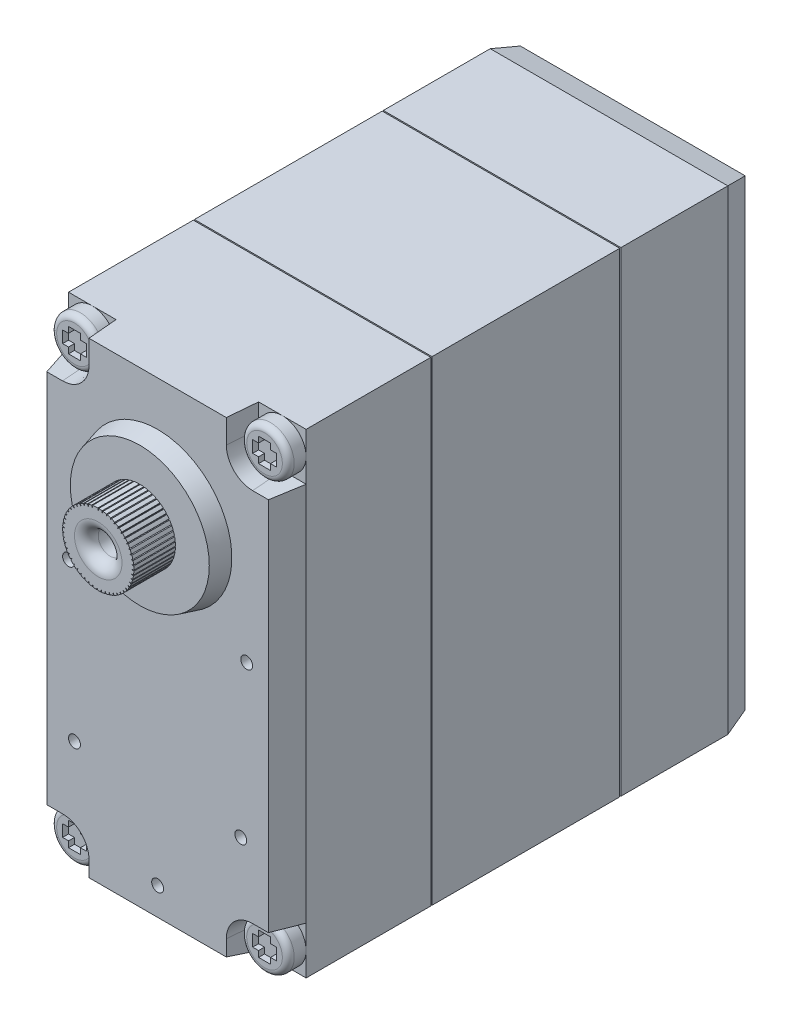
SolidWorks part; units mm, degrees
ref_plane "Front Plane" through (0, 0, 0) normal (0, 0, 1) x (1, 0, 0)
ref_plane "Top Plane" through (0, 0, 0) normal (0, 1, 0) x (1, 0, 0)
ref_plane "Right Plane" through (0, 0, 0) normal (1, 0, 0) x (0, 0, -1)
sketch "Sketch1" plane through (0, 0, 0) normal (0, 0, 1) x (1, 0, 0)
  line L1 (10, 20) -> (-10, 20)
  line L2 (10, 20) -> (10, -20)
  line L3 (10, -20) -> (-10, -20)
  line L4 (-10, 20) -> (-10, -20)
  line L5 (10, 20) -> (-10, -20) construction
  line L6 (10, -20) -> (-10, 20) construction
  point P0 (0, 0)
  dimension "D1" = 20
  dimension "D2" = 40
extrude "Boss-Extrude1" add sketch "Sketch1" along normal blind 40
sketch "Sketch2" plane through (0, 0, 40) normal (0, 0, 1) x (1, 0, 0)
  circle A0 centre (0, 10) radius 3
extrude "Boss-Extrude2" add sketch "Sketch2" along normal blind 5
sketch "Sketch3" plane through (0, 0, 40) normal (0, 0, 1) x (1, 0, 0)
  circle A0 centre (0, 10) radius 6.25
  dimension "D1" = 12.5
extrude "Boss-Extrude3" add sketch "Sketch3" along normal blind 1.5
sketch "Sketch4" plane through (0, 0, 0) normal (0, 0, -1) x (-1, 0, 0)
  circle A0 centre (0, 10) radius 3
extrude "Boss-Extrude4" add sketch "Sketch4" along normal blind 5
sketch "Sketch5" plane through (0, 0, 0) normal (0, 0, -1) x (-1, 0, 0)
  circle A0 centre (0, 10) radius 6.25
extrude "Boss-Extrude5" add sketch "Sketch5" along normal blind 1.5
chamfer "Chamfer1" distance 1.5 angle 15 2 edges at (6.25, 10, 41.5) (-6.25, 10, -1.5) first distance on face at (6.25, 10, 41.5) first distance on face at (-6.25, 10, -1.5)
sketch "Sketch6" plane through (0, 0, 40) normal (0, 0, 1) x (1, 0, 0)
  circle A0 centre (0, 10) radius 1
extrude "Cut-Extrude1" cut sketch "Sketch6" along normal blind 8.5
sketch "Sketch7" plane through (0, 0, 0) normal (0, 0, -1) x (-1, 0, 0)
  circle A0 centre (0, 10) radius 1
extrude "Cut-Extrude2" cut sketch "Sketch7" along normal blind 8.5
fillet "Fillet1" radius 0.2 1 edges at (-3, 10, -5)
sketch "Sketch8" plane through (0, 0, 0) normal (0, 0, -1) x (-1, 0, 0)
  line L5 (7.5, -2.5) -> (-7.5, -17.5) construction
  line L6 (7.5, -17.5) -> (-7.5, -2.5) construction
  circle A0 centre (-7.5, -17.5) radius 0.5
  circle A1 centre (7.5, -17.5) radius 0.5
  circle A2 centre (7.5, -2.5) radius 0.5
  circle A3 centre (-7.5, -2.5) radius 0.5
  point P0 (0, -10)
  dimension "D2" = 15
  dimension "D3" = 15
extrude "Cut-Extrude3" cut sketch "Sketch8" against normal blind 1
sketch "Sketch9" plane through (0, 0, 40) normal (0, 0, 1) x (1, 0, 0)
  circle A1 centre (-7, -10) radius 0.5
  circle A2 centre (7, -10) radius 0.5
  circle A3 centre (0, -17) radius 0.5
  circle A4 centre (-7.5, 3) radius 0.5
  circle A5 centre (7.5, 3) radius 0.5
  point P12 (0, -10)
  point P15 (0, -10)
extrude "Cut-Extrude4" cut sketch "Sketch9" against normal blind 1
sketch "Sketch10" plane through (0, 0, 41.5) normal (0, 0, 1) x (1, 0, 0)
  line L3 (-0.0094, 12.8532) -> (-0.0352, 12.9998)
  line L4 (0.0103, 12.853) -> (0.0388, 12.9997)
  arc A4 (0.0388, 12.9997) -> (-0.0352, 12.9998) centre (0, 10) ccw
  arc A5 (-0.0094, 12.8532) -> (0.0103, 12.853) centre (0.0005, 12.8549) ccw
  dimension "D1" = 0.01
extrude "Cut-Extrude6" cut sketch "Sketch10" along normal blind 10
ref_axis "Axis1" through (0, 10, 45) along (0, 0, -1)
pattern_circular "CirPattern1" count 51 every 7 about axis through (0, 10, 45) along (0, 0, -1) of "Cut-Extrude6"
fillet "Fillet2" radius 1 1 edges at (1, 10, 45)
chamfer "Chamfer2" distance 2.5 angle 15 3 edges at (10, 0, 40) (0, -20, 40) (-10, 0, 40) first distance on face at (10, 0, 20) first distance on face at (0, -20, 20) first distance on face at (-10, 0, 20)
chamfer "Chamfer3" distance 2 angle 15 4 edges at (0, 20, 0) (10, 0, 0) (0, -20, 0) (-10, 0, 0) first distance on face at (0, 20, 25.8333) first distance on face at (10, 0, 18.75) first distance on face at (0, -20, 18.75) first distance on face at (-10, 0, 18.75)
sketch "Sketch11" plane through (0, 0, 40) normal (0, 0, 1) x (1, 0, 0)
  line L0 (-10, -20) -> (-10, -16)
  line L1 (-10, 20) -> (-10, -20) construction
  line L2 (-10, -16) -> (-8, -16)
  line L3 (-6, -18) -> (-6, -20)
  line L4 (-10, -20) -> (10, -20) construction
  line L5 (-6, -20) -> (-10, -20)
  line L8 (-6, 20) -> (-10, 20)
  line L9 (-6, 18) -> (-6, 20)
  line L10 (-10, 16) -> (-8, 16)
  line L11 (-10, 20) -> (-10, 16)
  line L12 (10, 20) -> (10, 16)
  line L13 (10, 16) -> (8, 16)
  line L14 (6, 18) -> (6, 20)
  line L15 (6, 20) -> (10, 20)
  line L16 (6, -20) -> (10, -20)
  line L17 (6, -18) -> (6, -20)
  line L18 (10, -16) -> (8, -16)
  line L19 (10, -20) -> (10, -16)
  arc A0 (-6, -18) -> (-8, -16) centre (-8, -18) ccw
  arc A1 (-6, 18) -> (-8, 16) centre (-8, 18) cw
  arc A2 (6, 18) -> (8, 16) centre (8, 18) ccw
  arc A3 (6, -18) -> (8, -16) centre (8, -18) cw
extrude "Cut-Extrude7" cut sketch "Sketch11" against normal blind 2.5
chamfer "Chamfer4" distance 2.5 angle 5 12 edges at (-8.6651, 16, 40) (-6, 19, 40) (-6.5858, 16.5858, 40) (-6, -18.6651, 40) (-8.6651, -16, 40) (-6.5858, -16.5858, 40) (8.6651, -16, 40) (6, -18.6651, 40) (6.5858, -16.5858, 40) (6, 19, 40) (8.6651, 16, 40) (6.5858, 16.5858, 40) first distance on face at (-8.8325, 16, 38.75) first distance on face at (-6, 19, 38.75) first distance on face at (-6.7929, 16.7929, 38.75) first distance on face at (-6, -18.8325, 38.75) first distance on face at (-8.8325, -16, 38.75) first distance on face at (-6.7929, -16.7929, 38.75) first distance on face at (8.8325, -16, 38.75) first distance on face at (6, -18.8325, 38.75) first distance on face at (6.7929, -16.7929, 38.75) first distance on face at (6, 19, 38.75) first distance on face at (8.8325, 16, 38.75) first distance on face at (6.7929, 16.7929, 38.75)
sketch "Sketch12" plane through (0, 0, 37.5) normal (0, 0, 1) x (1, 0, 0)
  circle A0 centre (8, -18) radius 2
  circle A1 centre (-8, -18) radius 2
  circle A2 centre (-8, 18) radius 2
  circle A3 centre (8, 18) radius 2
extrude "Boss-Extrude6" add sketch "Sketch12" along normal blind 1.5
fillet "Fillet3" radius 0.5 4 edges at (-6, 18, 39) (6, 18, 39) (10, -18, 39) (-10, -18, 39)
sketch "Sketch13" plane through (0, 0, 39) normal (0, 0, 1) x (1, 0, 0)
  line L0 (-8.5, -17) -> (-7.5, -17)
  line L1 (-7, -17.5) -> (-7, -18.5)
  line L2 (-8.5, -17) -> (-8.5, -17.5)
  line L3 (-7, -17.5) -> (-7.5, -17.5)
  line L4 (-7.5, -17) -> (-7.5, -17.5)
  line L5 (-7, -18.5) -> (-7.5, -18.5)
  line L6 (-7.5, -19) -> (-8.5, -19)
  line L7 (-9, -18.5) -> (-9, -17.5)
  line L8 (-8.5, -18.5) -> (-8.5, -19)
  line L9 (-8.5, -17.5) -> (-9, -17.5)
  line L10 (-7.5, -18.5) -> (-7.5, -19)
  line L11 (-8.5, -18.5) -> (-9, -18.5)
  line L14 (8.5, -18.5) -> (9, -18.5)
  line L15 (7.5, -18.5) -> (7.5, -19)
  line L16 (8.5, -17.5) -> (9, -17.5)
  line L17 (8.5, -18.5) -> (8.5, -19)
  line L18 (9, -18.5) -> (9, -17.5)
  line L19 (7.5, -19) -> (8.5, -19)
  line L20 (7, -18.5) -> (7.5, -18.5)
  line L21 (7.5, -17) -> (7.5, -17.5)
  line L22 (7, -17.5) -> (7.5, -17.5)
  line L23 (8.5, -17) -> (8.5, -17.5)
  line L24 (7, -17.5) -> (7, -18.5)
  line L25 (8.5, -17) -> (7.5, -17)
  line L26 (8.5, 17) -> (7.5, 17)
  line L27 (7, 17.5) -> (7, 18.5)
  line L28 (8.5, 17) -> (8.5, 17.5)
  line L29 (7, 17.5) -> (7.5, 17.5)
  line L30 (7.5, 17) -> (7.5, 17.5)
  line L31 (7, 18.5) -> (7.5, 18.5)
  line L32 (7.5, 19) -> (8.5, 19)
  line L33 (9, 18.5) -> (9, 17.5)
  line L34 (8.5, 18.5) -> (8.5, 19)
  line L35 (8.5, 17.5) -> (9, 17.5)
  line L36 (7.5, 18.5) -> (7.5, 19)
  line L37 (8.5, 18.5) -> (9, 18.5)
  line L38 (-8.5, 18.5) -> (-9, 18.5)
  line L39 (-7.5, 18.5) -> (-7.5, 19)
  line L40 (-8.5, 17.5) -> (-9, 17.5)
  line L41 (-8.5, 18.5) -> (-8.5, 19)
  line L42 (-9, 18.5) -> (-9, 17.5)
  line L43 (-7.5, 19) -> (-8.5, 19)
  line L44 (-7, 18.5) -> (-7.5, 18.5)
  line L45 (-7.5, 17) -> (-7.5, 17.5)
  line L46 (-7, 17.5) -> (-7.5, 17.5)
  line L47 (-8.5, 17) -> (-8.5, 17.5)
  line L48 (-7, 17.5) -> (-7, 18.5)
  line L49 (-8.5, 17) -> (-7.5, 17)
  point P6 (-8, -18)
  point P9 (-8, -18)
  point P31 (8, -18)
  point P56 (8, 18)
  point P57 (-8, 18)
extrude "Cut-Extrude8" cut sketch "Sketch13" against normal blind 0.5
ref_plane "Plane1" through (0, 0, 27) normal (0, 0, 1) x (1, 0, 0)
sketch "Sketch14" plane through (0, 0, 27) normal (0, 0, 1) x (1, 0, 0)
  line L0 (-9.9, 19.9) -> (-9.9, -19.9)
  line L1 (-10, 20) -> (10, 20)
  line L2 (-10, 20) -> (-10, -20)
  line L3 (-10, -20) -> (10, -20)
  line L4 (10, 20) -> (10, -20)
  line L5 (-9.9, -19.9) -> (9.9, -19.9)
  line L6 (9.9, 19.9) -> (9.9, -19.9)
  line L7 (-9.9, 19.9) -> (9.9, 19.9)
  dimension "D1" = 0.1
extrude "Cut-Extrude9" cut sketch "Sketch14" against normal blind 0.1
ref_plane "Plane2" through (0, 0, 11) normal (0, 0, -1) x (-1, 0, 0)
sketch "Sketch15" plane through (0, 0, 11) normal (0, 0, -1) x (-1, 0, 0)
  line L0 (-9.9, 19.9) -> (-9.9, -19.9)
  line L1 (-10, 20) -> (10, 20)
  line L2 (-10, 20) -> (-10, -20)
  line L3 (-10, -20) -> (10, -20)
  line L4 (10, 20) -> (10, -20)
  line L5 (-9.9, -19.9) -> (9.9, -19.9)
  line L6 (9.9, 19.9) -> (9.9, -19.9)
  line L7 (-9.9, 19.9) -> (9.9, 19.9)
  dimension "D1" = 0.1
extrude "Cut-Extrude10" cut sketch "Sketch15" against normal blind 0.1
